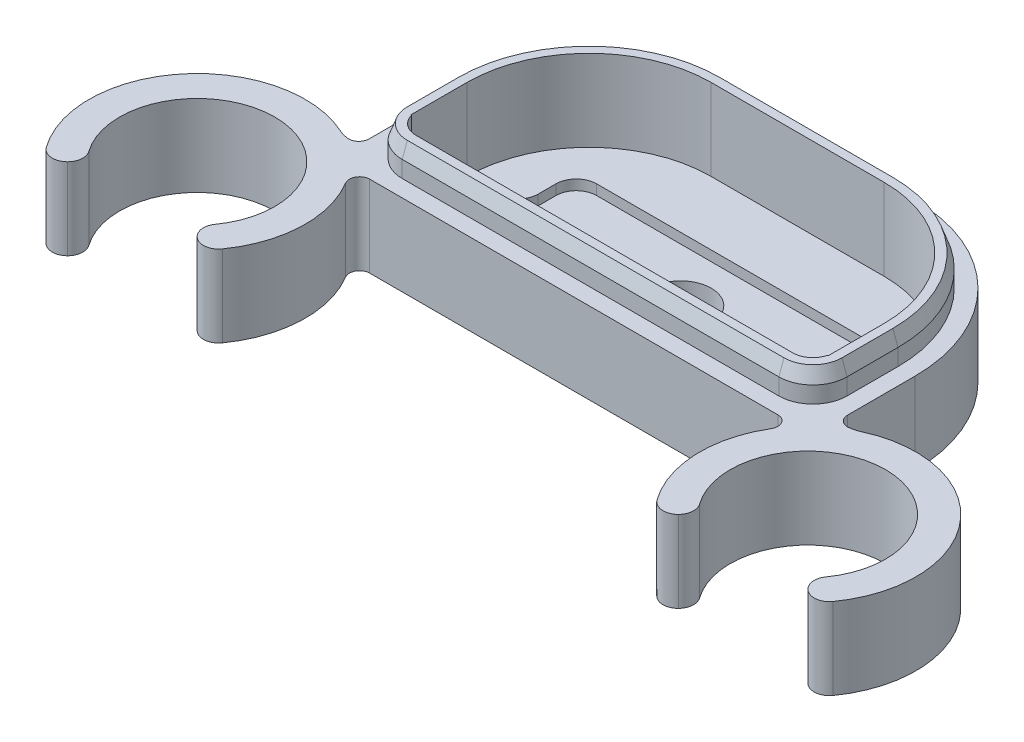
SolidWorks part; units mm, degrees
ref_plane "Front Plane" through (0, 0, 0) normal (0, 0, 1) x (1, 0, 0)
ref_plane "Top Plane" through (0, 0, 0) normal (0, 1, 0) x (1, 0, 0)
ref_plane "Right Plane" through (0, 0, 0) normal (1, 0, 0) x (0, 0, -1)
sketch "Sketch1" plane through (0, 0, 0) normal (0, 1, 0) x (1, 0, 0)
  line L0 (-23.5, 12.5) -> (23.5, 12.5)
  line L1 (-20.5, -9.5) -> (20.5, -9.5) construction
  line L2 (-20.5, -9.5) -> (-20.5, 9.5) construction
  line L3 (-20.5, 9.5) -> (20.5, 9.5) construction
  line L4 (20.5, -9.5) -> (20.5, 9.5) construction
  line L5 (-20.5, -9.5) -> (20.5, 9.5) construction
  line L6 (-20.5, 9.5) -> (20.5, -9.5) construction
  line L7 (23.5, -12.5) -> (23.5, 12.5)
  line L8 (-23.5, -12.5) -> (23.5, -12.5)
  line L9 (-23.5, -12.5) -> (-23.5, 12.5)
  point P0 (0, 0)
  dimension "D1" = 19
  dimension "D2" = 41
  dimension "D3" = 3
extrude "Boss-Extrude1" add sketch "Sketch1" along normal blind 8
shell "Shell1" thickness 3 removed face at (0, 8, 0)
sketch "Sketch2" plane through (0, 0, 0) normal (0, 1, 0) x (1, 0, 0)
  line L0 (0, 0) -> (-30, 0) construction
  line L1 (0, 0) -> (0, 6.7838) construction
  circle A0 centre (-30, 0) radius 7.625
  circle A1 centre (30, 0) radius 7.625
  dimension "D1" = 15.25
  dimension "D2" = 30
extrude "Cut-Extrude3" [suppressed] cut sketch "Sketch2" along normal through all
sketch "Sketch3" [suppressed] plane through (0, 0, 0) normal (0, 1, 0) x (1, 0, 0)
  line L0 (-20.5, 4.7582) -> (-20.5, -4.7582)
  line L1 (-26.5, 10.032) -> (-26.5, 6.7743)
  line L2 (-26.5, -6.7743) -> (-26.5, -10.032)
  line L3 (-23.5, 12.5) -> (-23.5, 3.9863) construction
  line L4 (0, 0) -> (0, 12.5) construction
  line L5 (23.5, 12.5) -> (-23.5, 12.5) construction
  line L6 (26.5, -6.7743) -> (26.5, -10.032)
  line L7 (26.5, 10.032) -> (26.5, 6.7743)
  line L8 (20.5, 4.7582) -> (20.5, -4.7582)
  arc A0 (-26.5, -6.7743) -> (-26.5, 6.7743) centre (-30, 0) ccw
  arc A1 (-20.5, 4.7582) -> (-26.5, 10.032) centre (-30, 0) ccw
  arc A2 (-26.5, -10.032) -> (-20.5, -4.7582) centre (-30, 0) ccw
  arc A3 (26.5, -10.032) -> (20.5, -4.7582) centre (30, 0) cw
  arc A4 (20.5, 4.7582) -> (26.5, 10.032) centre (30, 0) cw
  arc A5 (26.5, -6.7743) -> (26.5, 6.7743) centre (30, 0) cw
  dimension "D1" = 3
  dimension "D4" = 7.625
  dimension "D2" = 3
  dimension "D3" = 30
extrude "Boss-Extrude2" [suppressed] add sketch "Sketch3" along normal blind 67
fillet "Fillet1" [suppressed] radius 1
sketch "Sketch4" plane through (0, 0, 0) normal (0, -1, 0) x (1, 0, 0)
  line L0 (0, 12.5) -> (0, 2) construction
  line L1 (-23.5, 12.5) -> (23.5, 12.5) construction
  line L2 (6, 6.75) -> (6, 2.25)
  line L3 (-15.5, 6.75) -> (-6, 6.75)
  line L4 (-15.5, 6.75) -> (-15.5, 2.25)
  line L5 (-15.5, 2.25) -> (-6, 2.25)
  line L6 (-6, 6.75) -> (-6, 2.25)
  line L7 (15.5, 2.25) -> (6, 2.25)
  line L8 (15.5, 6.75) -> (15.5, 2.25)
  line L9 (15.5, 6.75) -> (6, 6.75)
  circle A0 centre (0, 2) radius 3
  dimension "D2" = 6
  dimension "D1" = 10.5
  dimension "D3" = 15.5
  dimension "D4" = 5.75
  dimension "D5" = 4.5
extrude "Cut-Extrude4" cut sketch "Sketch4" against normal through all
fillet "Fillet2" radius 12 2 edges at (20.5, 5.5, -9.5) (-20.5, 5.5, -9.5)
fillet "Fillet3" radius 15 2 edges at (23.5, 4, -12.5) (-23.5, 4, -12.5)
sketch "Sketch5" plane through (0, 0, 0) normal (0, 1, 0) x (1, 0, 0)
  line L0 (0, -12.5) -> (0, -19.5) construction
  line L1 (-23.5, -12.5) -> (23.5, -12.5) construction
  line L2 (0, -19.5) -> (-30, -19.5) construction
  line L3 (-30, -19.5) -> (0, 12.5) construction
  line L4 (8.5, 12.5) -> (-8.5, 12.5) construction
  line L5 (-24.1091, -10.6576) -> (-23.0238, -9.5)
  line L6 (-18.8171, -9.5) -> (-23.0238, -9.5)
  line L7 (-21.8511, -12.682) -> (-18.8171, -9.5)
  line L8 (21.8511, -12.682) -> (18.8171, -9.5)
  line L9 (18.8171, -9.5) -> (23.0238, -9.5)
  line L10 (24.1091, -10.6576) -> (23.0238, -9.5)
  line L11 (-20.5, -9.5) -> (20.5, -9.5) construction
  circle A0 centre (-30, -19.5) radius 7.625
  arc A1 (-24.1091, -10.6576) -> (-21.8511, -12.682) centre (-30, -19.5) ccw
  arc A2 (24.1091, -10.6576) -> (21.8511, -12.682) centre (30, -19.5) cw
  circle A3 centre (30, -19.5) radius 7.625
  dimension "D3" = 15.25
  dimension "D4" = 21.25
  dimension "D1" = 7
  dimension "D2" = 30
  dimension "D5" = 1.75
  dimension "D6" = 0
extrude "Boss-Extrude3" add sketch "Sketch5" along normal blind 8
fillet "Fillet7" radius 2 2 edges at (-20.5, 5.5, 9.5) (20.5, 5.5, 9.5)
fillet "Fillet9" radius 3 2 edges at (-24.1091, 4, 10.6576) (24.1091, 4, 10.6576)
fillet "Fillet10" radius 3 2 edges at (-21.8511, 4, 12.682) (21.8511, 4, 12.682)
sketch "Sketch6" plane through (0, 8, 0) normal (0, 1, 0) x (1, 0, 0)
  line L11 (-21.85, -2.5) -> (-21.85, -7.5)
  line L12 (-18.5, -9.5) -> (18.5, -9.5)
  line L13 (-20.5, -2.5) -> (-20.5, -7.5)
  line L14 (8.5, 9.5) -> (-8.5, 9.5)
  line L15 (-18.5, -9.5) -> (18.5, -9.5)
  line L16 (-20.5, -2.5) -> (-20.5, -7.5)
  line L17 (8.5, 9.5) -> (-8.5, 9.5)
  line L18 (20.5, -7.5) -> (20.5, -2.5)
  line L19 (20.5, -7.5) -> (20.5, -2.5)
  line L20 (-18.5, -10.85) -> (18.5, -10.85)
  line L21 (21.85, -7.5) -> (21.85, -2.5)
  line L22 (8.5, 10.85) -> (-8.5, 10.85)
  arc A8 (-20.5, -7.5) -> (-18.5, -9.5) centre (-18.5, -7.5) ccw
  arc A9 (-8.5, 9.5) -> (-20.5, -2.5) centre (-8.5, -2.5) ccw
  arc A10 (-20.5, -7.5) -> (-18.5, -9.5) centre (-18.5, -7.5) ccw
  arc A11 (-8.5, 9.5) -> (-20.5, -2.5) centre (-8.5, -2.5) ccw
  arc A14 (-8.5, 10.85) -> (-21.85, -2.5) centre (-8.5, -2.5) ccw
  arc A15 (-21.85, -7.5) -> (-18.5, -10.85) centre (-18.5, -7.5) ccw
  arc A16 (20.5, -2.5) -> (8.5, 9.5) centre (8.5, -2.5) ccw
  arc A17 (18.5, -9.5) -> (20.5, -7.5) centre (18.5, -7.5) ccw
  arc A18 (20.5, -2.5) -> (8.5, 9.5) centre (8.5, -2.5) ccw
  arc A19 (18.5, -9.5) -> (20.5, -7.5) centre (18.5, -7.5) ccw
  arc A20 (18.5, -10.85) -> (21.85, -7.5) centre (18.5, -7.5) ccw
  arc A21 (21.85, -2.5) -> (8.5, 10.85) centre (8.5, -2.5) ccw
  dimension "D1" = 0
  dimension "D2" = 0
  dimension "D3" = 1.35
extrude "Boss-Extrude4" add sketch "Sketch6" along normal blind 3
fillet "Fillet11" radius 1 4 edges at (21.6776, 4, 12.5) (23.5, 4, 10.008) (-21.6776, 4, 12.5) (-23.5, 4, 10.008)
chamfer "Chamfer1" distance 0.5 angle 70 8 edges at (0, 11, 10.85) (20.8688, 11, 9.8688) (21.85, 11, 5) (17.9399, 11, -6.9399) (0, 11, -10.85) (-17.9399, 11, -6.9399) (-21.85, 11, 5) (-20.8688, 11, 9.8688) first distance on face at (0, 11, 1.9822)
sketch "Sketch7" plane through (0, 3, 0) normal (0, 1, 0) x (1, 0, 0)
  line L0 (-20.5, -2.5) -> (-20.5, -7.5) construction
  line L2 (-20.5, -6.75) -> (-20.5, -2.5)
  line L3 (-20.5, -2.5) -> (-17.5, -2.5)
  line L4 (20.5, -6.75) -> (20.5, -2.5)
  line L5 (-15.5, -6.75) -> (-15.5, -2.25) construction
  line L6 (-18.5, -9.5) -> (18.5, -9.5) construction
  line L7 (-15.5, -0.5) -> (-15.5, 1.25)
  line L8 (-13.5, 3.25) -> (13.5, 3.25)
  line L9 (15.5, -0.5) -> (15.5, 1.25)
  line L10 (15.5, -2.25) -> (15.5, -6.75) construction
  line L11 (17.5, -2.5) -> (20.5, -2.5)
  line L13 (-20.5, -6.75) -> (-20.5, -8)
  line L14 (-20.5, -8) -> (20.5, -8)
  line L15 (20.5, -6.75) -> (20.5, -8)
  arc A0 (-15.5, 1.25) -> (-13.5, 3.25) centre (-13.5, 1.25) cw
  arc A1 (13.5, 3.25) -> (15.5, 1.25) centre (13.5, 1.25) cw
  arc A2 (17.5, -2.5) -> (15.5, -0.5) centre (17.5, -0.5) cw
  arc A3 (-17.5, -2.5) -> (-15.5, -0.5) centre (-17.5, -0.5) ccw
  point P23 (-15.5, -2.5)
  dimension "D2" = 2
  dimension "D3" = 1.5
extrude "Cut-Extrude5" cut sketch "Sketch7" against normal blind 1 and the other way blind 10
sketch "Sketch8" plane through (0, 0, 0) normal (0, -1, 0) x (1, 0, 0)
  line L0 (-30, 19.5) -> (-30, 34.7163) construction
  line L1 (-30, 19.5) -> (-42.6794, 32.1794)
  line L2 (-30, 19.5) -> (-17.3206, 32.1794)
  line L3 (-42.6794, 32.1794) -> (-17.3206, 32.1794)
  line L4 (0, 0) -> (0, 21.8483) construction
  line L5 (30, 19.5) -> (30, 34.7163) construction
  line L6 (42.6794, 32.1794) -> (17.3206, 32.1794)
  line L7 (30, 19.5) -> (17.3206, 32.1794)
  line L8 (30, 19.5) -> (42.6794, 32.1794)
  dimension "D1" = 45
extrude "Cut-Extrude6" cut sketch "Sketch8" against normal blind 10
fillet "Fillet12" radius 1.5 8 edges at (37.513, 4, 27.013) (35.3917, 4, 24.8917) (24.6083, 4, 24.8917) (22.487, 4, 27.013) (-24.6083, 4, 24.8917) (-22.487, 4, 27.013) (-35.3917, 4, 24.8917) (-37.513, 4, 27.013)
